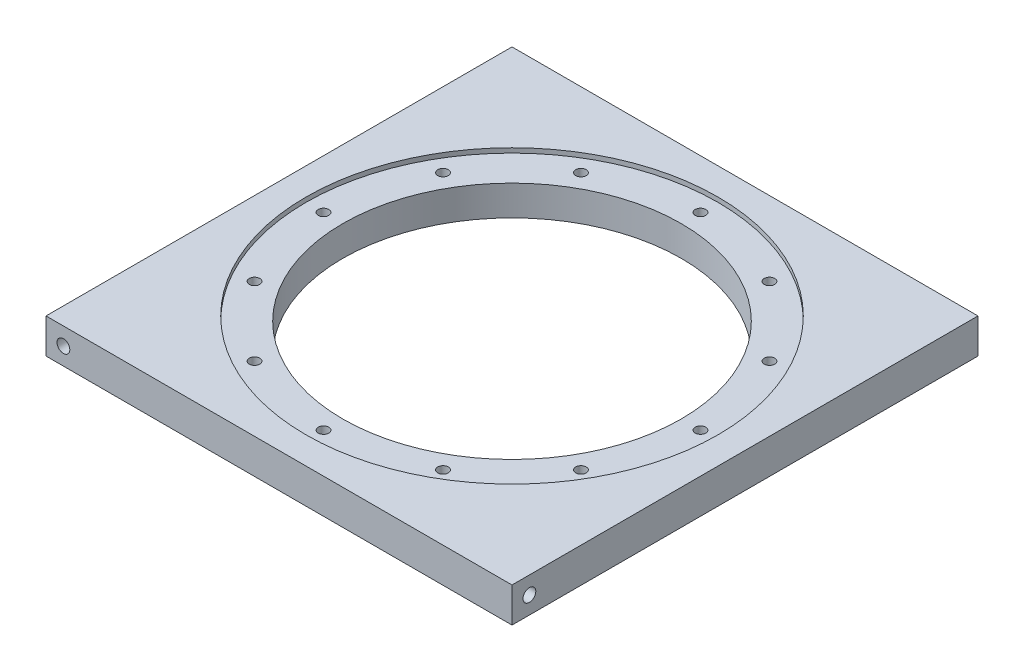
SolidWorks part; units mm, degrees
material "6061-T6 (SS)"
ref_plane "Front Plane" through (0, 0, 0) normal (0, 0, 1) x (1, 0, 0)
ref_plane "Top Plane" through (0, 0, 0) normal (0, 1, 0) x (1, 0, 0)
ref_plane "Right Plane" through (0, 0, 0) normal (1, 0, 0) x (0, 0, -1)
sketch "Sketch1" plane through (0, 0, 0) normal (0, 1, 0) x (1, 0, 0)
  line L5 (0, 0) -> (127.635, 0)
  line L6 (0, 0) -> (0, 127.635)
  line L7 (0, 127.635) -> (127.635, 127.635)
  line L8 (127.635, 0) -> (127.635, 127.635)
  dimension "D1" = 127.635
  dimension "D2" = 127.635
extrude "Boss-Extrude1" add sketch "Sketch1" along normal blind 9.525 contours L5 L8 L7 L6
sketch "Sketch5" plane through (0, 9.525, 0) normal (0, 1, 0) x (1, 0, 0)
  line L0 (63.8175, 0) -> (63.8175, 127.635) construction
  line L3 (0, 0) -> (127.635, 0) construction
  line L8 (0, 127.635) -> (127.635, 127.635) construction
  circle A0 centre (63.8175, 63.8175) radius 46.355
  dimension "D1" = 92.71
extrude "Cut-Extrude1" cut sketch "Sketch5" against normal blind 9.525 contours L0 A0 | A0 L0
sketch "Sketch6" plane through (127.635, 0, 0) normal (1, 0, 0) x (0, 0, -1)
  circle A0 centre (4.7625, 4.7625) radius 1.7526
  dimension "D1" = 3.5052
extrude "6-32 hole1" cut sketch "Sketch6" against normal blind 6.35
sketch "Sketch7" plane through (0, 0, -127.635) normal (0, 0, -1) x (-1, 0, 0)
  circle A0 centre (-122.8725, 4.7625) radius 1.7526
  dimension "D1" = 3.5052
sketch "Sketch8" plane through (0, 0, 0) normal (-1, 0, 0) x (0, 0, 1)
  circle A0 centre (-122.8725, 4.7625) radius 1.7526
  dimension "D1" = 3.5052
sketch "Sketch9" plane through (0, 0, 0) normal (0, 0, 1) x (1, 0, 0)
  circle A0 centre (4.7625, 4.7625) radius 1.7526
  dimension "D1" = 3.5052
extrude "6-32 hole2" cut sketch "Sketch7" against normal blind 6.35
extrude "6-32 hole3" cut sketch "Sketch8" against normal blind 6.35
extrude "6-32 hole4" cut sketch "Sketch9" against normal blind 6.35
sketch "Sketch11" plane through (0, 9.525, 0) normal (0, 1, 0) x (1, 0, 0)
  line L0 (63.8175, 63.8175) -> (63.8175, 115.443) construction
  circle A0 centre (63.8175, 115.443) radius 1.4351
  dimension "D2" = 2.8702
  dimension "D1" = 51.6255
extrude "Cut-Extrude3" cut sketch "Sketch11" against normal through all contours A0
pattern_circular "CirPattern1" count 12 over 360 about axis through (63.8175, 9.525, -63.8175) along (0, 1, 0) of "Cut-Extrude3"
sketch "Sketch12" plane through (0, 9.525, 0) normal (0, 1, 0) x (1, 0, 0)
  circle A0 centre (63.8175, 63.8175) radius 56.4198
  dimension "D1" = 112.8395
extrude "Cut-Extrude4" cut sketch "Sketch12" against normal blind 1.27
